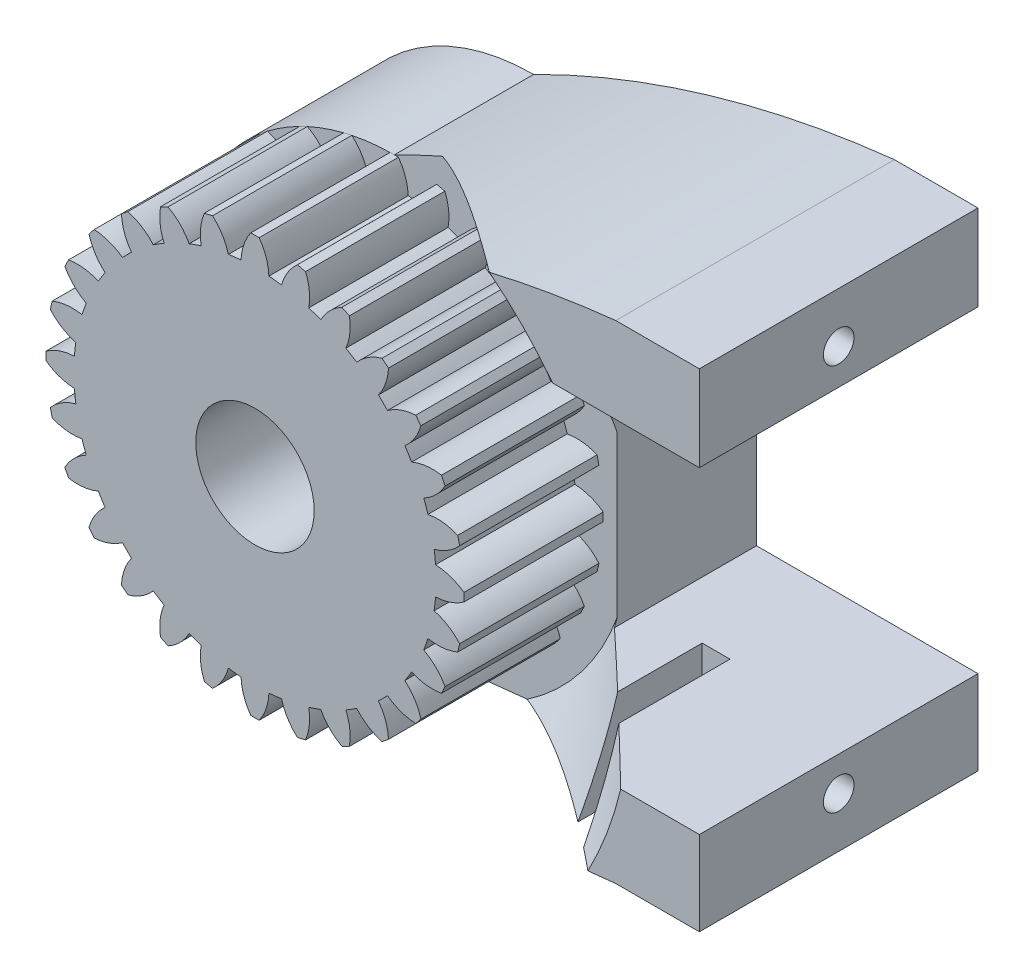
SolidWorks part; units mm, degrees
ref_plane "Front Plane" through (0, 0, 0) normal (0, 0, 1) x (1, 0, 0)
ref_plane "Top Plane" through (0, 0, 0) normal (0, 1, 0) x (1, 0, 0)
ref_plane "Right Plane" through (0, 0, 0) normal (1, 0, 0) x (0, 0, -1)
sketch "Sketch2" plane through (0, 0, 0) normal (0, 0, 1) x (1, 0, 0)
  line L0 (0, 0) -> (0, 18.136) construction
  line L1 (0.3, 15) -> (-0.3, 15)
  circle A0 centre (0, 0) radius 13
  circle A1 centre (0, 0) radius 4.25
  circle A2 centre (0, 0) radius 15 construction
  arc A3 (-0.3, 15) -> (-1, 12.9615) centre (2.738, 12.8174) ccw
  arc A4 (0.3, 15) -> (1, 12.9615) centre (-2.738, 12.8174) cw
  point P11 (-0.8, 14.0322)
  point P13 (0, 15)
  dimension "D1" = 26
  dimension "D2" = 8.5
  dimension "D6" = 0.8
  dimension "D7" = 30
  dimension "D4" = 0.6
  dimension "D5" = 1
  dimension "D3" = 2
extrude "Boss-Extrude1" add sketch "Sketch2" along normal blind 10 contours A0 A1 region at (9.2696, 8.582, 0)
extrude "Boss-Extrude2" add sketch "Sketch2<3>" along normal blind 10 contours A4 L1 A3 A0 region at (0, 13.8421, 0)
sketch "Sketch2<3>" plane through (0, 0, 0) normal (0, 0, 1) x (1, 0, 0) same geometry as "Sketch2"
pattern_circular "CirPattern1" count 28 over 360 about axis through (0, 0, 10) along (0, 0, 1) of "Boss-Extrude2"
sketch "Sketch3" plane through (0, 0, 10) normal (0, 0, 1) x (1, 0, 0)
  circle A0 centre (0, 0) radius 15
  circle A1 centre (0, 0) radius 7.5
  dimension "D1" = 30
  dimension "D2" = 15
extrude "Boss-Extrude3" add sketch "Sketch3" along normal blind 10
sketch "Sketch5" plane through (0, 0, 10) normal (0, 0, 1) x (1, 0, 0)
  circle A0 centre (0, 0) radius 4.25
  circle A1 centre (0, 0) radius 7.5
extrude "Boss-Extrude4" add sketch "Sketch5" along normal blind 5
sketch "Sketch6" plane through (0, 0, 20) normal (0, 0, 1) x (1, 0, 0)
  line L0 (0, 0) -> (16, 0) construction
  line L4 (42.95, -6.1) -> (16.2, -6.1) construction
  line L5 (72.2526, -52.0805) -> (45.5026, -52.0805)
  line L6 (72.2526, -52.0805) -> (72.2526, -39.8805)
  line L7 (72.2526, -39.8805) -> (45.5026, -39.8805)
  line L8 (45.5026, -52.0805) -> (45.5026, -39.8805)
  line L9 (72.2526, -52.0805) -> (45.5026, -39.8805) construction
  line L10 (72.2526, -39.8805) -> (45.5026, -52.0805) construction
  line L11 (42.95, -6.1) -> (42.95, 16.4) construction
  line L12 (42.95, 16.4) -> (16.2, 16.4) construction
  line L13 (16.2, -6.1) -> (16.2, 16.4) construction
  line L14 (42.95, -6.1) -> (16.2, 16.4) construction
  line L15 (42.95, 16.4) -> (16.2, -6.1) construction
  line L16 (0, 5.15) -> (50.833, 5.15) construction
  line L17 (0, 9.8857) -> (0, -10.1143) construction
  line L18 (43.15, 16.5) -> (16, 16.5)
  line L19 (16, -6.3) -> (16, 16.5)
  line L20 (43.15, -6.3) -> (16, -6.3)
  line L21 (43.15, -6.3) -> (43.15, 16.5)
  line L22 (31.5314, 22.65) -> (31.5314, 20.5) construction
  line L23 (31.9, -12.35) -> (25.9, -12.35)
  line L24 (31.9, -12.35) -> (31.9, 22.65)
  line L25 (31.9, 22.65) -> (25.9, 22.65)
  line L26 (25.9, -12.35) -> (25.9, 22.65)
  line L27 (31.9, -12.35) -> (25.9, 22.65) construction
  line L28 (31.9, 22.65) -> (25.9, -12.35) construction
  line L29 (18.9976, 0) -> (49.2209, 0) construction
  line L30 (25.9, -12.35) -> (2.0604, -14.8578)
  line L31 (16, -6.3) -> (13.6129, -6.3)
  arc A1 (25.9, 22.65) -> (0, 15) centre (33.848, -51.9277) ccw
  arc A2 (0, 15) -> (0, -15) centre (0, 0) cw
  circle A3 centre (0, 0) radius 15 construction
  point P1 (58.8776, -45.9805)
  point P12 (29.575, 5.15)
  point P29 (28.9, 5.15)
  circle M3 centre (0, 0) radius 15
  dimension "D2" = 12.2
  dimension "D14" = 16
  dimension "D15" = 75
  dimension "D1" = 26.75
  dimension "D3" = 26.75
  dimension "D4" = 22.5
  dimension "D5" = 15.7
  dimension "D6" = 35
  dimension "D7" = 2.15
  dimension "D8" = 6
  dimension "D9" = 6.1
  dimension "D10" = 0.2
  dimension "D11" = 0.2
  dimension "D12" = 0.2
  dimension "D13" = 0.2
sketch "Sketch11" plane through (0, 0, 0) normal (0, 1, 0) x (1, 0, 0)
  line L0 (72.2526, -20) -> (45.5026, -20) construction
  line L1 (45.1876, -16.1) -> (18.4376, -16.1) construction
  line L2 (45.1876, -16.1) -> (45.1876, 6.4) construction
  line L3 (45.1876, 6.4) -> (18.4376, 6.4) construction
  line L4 (18.4376, -16.1) -> (18.4376, 6.4) construction
  line L5 (45.1876, -16.1) -> (18.4376, 6.4) construction
  line L6 (45.1876, 6.4) -> (18.4376, -16.1) construction
  line L7 (0, -4.85) -> (48.8951, -4.85) construction
  line L8 (0, 0) -> (0, -20) construction
  line L9 (0, -20) -> (16, -20) construction
  line L10 (45.3876, 6.6) -> (18.2376, 6.6)
  line L11 (18.2376, -16.3) -> (18.2376, 6.6)
  line L12 (45.3876, -16.3) -> (18.2376, -16.3)
  line L13 (45.3876, -16.3) -> (45.3876, 6.6)
  line L14 (33.7357, 11.2) -> (33.7357, 9.05) construction
  line L15 (34.1376, -20.9) -> (28.1376, -20.9)
  line L16 (34.1376, -20.9) -> (34.1376, 11.2)
  line L17 (34.1376, 11.2) -> (28.1376, 11.2)
  line L18 (28.1376, -20.9) -> (28.1376, 11.2)
  line L19 (34.1376, -20.9) -> (28.1376, 11.2) construction
  line L20 (34.1376, 11.2) -> (28.1376, -20.9) construction
  line L21 (17.0596, -10) -> (47.283, -10) construction
  point P0 (31.8126, -4.85)
  point P24 (31.1376, -4.85)
  dimension "D1" = 26.75
  dimension "D2" = 22.5
  dimension "D4" = 15.7
  dimension "D5" = 32.1
  dimension "D6" = 2.15
  dimension "D7" = 6
  dimension "D8" = 6.1
  dimension "D3" = 0.2
extrude "Boss-Extrude7" add sketch "Sketch6" against normal blind 10 contours L26 A1 L31 L19 L18 M3 | L26 L18 L24 L25 | L20 L31 L30 L26 M3 | L26 L23 L24 L20 region at (28.9, 19.575, 20) region at (14.6392, 14.3925, 20) region at (28.9, -9.325, 20) region at (17.5515, -10.1768, 20)
sketch "Sketch12" plane through (0, 0, 10) normal (0, 0, -1) x (-1, 0, 0)
  line L0 (-25.9, 22.65) -> (-31.9, 22.65)
  line L1 (-31.9, 22.65) -> (-31.9, 16.5)
  line L2 (-31.9, 16.5) -> (-16, 16.5)
  line L3 (-16, 16.5) -> (-16, 5.7446)
  line L4 (-16, -6.3) -> (-16, 16.5) construction
  line L5 (-16, -5.7446) -> (-16, -6.3)
  line L6 (-16, -6.3) -> (-31.9, -6.3)
  line L7 (-31.9, -6.3) -> (-31.9, -12.35)
  line L8 (-31.9, -12.35) -> (-25.9, -12.35)
  line L9 (-25.9, -12.35) -> (-9.5397, -14.071)
  line L10 (-25.9, -12.35) -> (-2.0604, -14.8578) construction
  circle A0 centre (0, 0) radius 17
  arc A1 (-25.9, 22.65) -> (-3.4659, 16.6429) centre (-33.848, -51.9277) cw
  arc A2 (0, 15) -> (-25.9, 22.65) centre (-33.848, -51.9277) ccw construction
  dimension "D1" = 34
extrude "Boss-Extrude8" add sketch "Sketch12" along normal blind 10 contours A1 L0 L1 L2 L3 A0 | A0 L5 L6 L7 L8 L9 region at (18.9294, 17.6106, 10) region at (22.2103, -9.7895, 10)
chamfer "Chamfer1" distance 10 angle 45 2 edges at (13.4314, -10.421, 0) (11.1546, 12.8287, 0)
mirror "Mirror1" about plane through (0, 0, 0) normal (0, 0, 1) of bodies 118
sketch "Sketch13" plane through (0, 0, 20) normal (0, 0, 1) x (1, 0, 0)
  line L1 (-37.7735, 30.5558) -> (48.8875, 30.5558)
  line L2 (-37.7735, 30.5558) -> (-37.7735, -27.2801)
  line L3 (-37.7735, -27.2801) -> (48.8875, -27.2801)
  line L4 (48.8875, 30.5558) -> (48.8875, -27.2801)
  line L5 (-37.7735, 30.5558) -> (48.8875, -27.2801) construction
  line L6 (-37.7735, -27.2801) -> (48.8875, 30.5558) construction
  point P0 (5.557, 1.6379)
extrude "Cut-Extrude1" cut sketch "Sketch13" against normal blind 20
sketch "Sketch14" plane through (31.9, 0, 0) normal (1, 0, 0) x (0, 0, -1)
  line L0 (10, 22.65) -> (10, -12.35) construction
  line L1 (20, 22.65) -> (0, 22.65) construction
  line L2 (20, -12.35) -> (0, -12.35) construction
  line L3 (10, 5.15) -> (21.6897, 5.15) construction
  line L4 (4.0163, 16.5) -> (20, 16.5) construction
  circle A0 centre (10, 19.05) radius 1.1
  circle A2 centre (10, -8.75) radius 1.1
  dimension "D3" = 2.2
  dimension "D1" = 6.15
  dimension "D2" = 27.8
extrude "Cut-Extrude2" cut sketch "Sketch14" against normal blind 2
sketch "Sketch15" plane through (0, -6.3, 0) normal (0, 1, 0) x (1, 0, 0)
  line L0 (31.9, 10) -> (29.1759, 10) construction
  line L1 (20.1, 12) -> (22.1, 12)
  line L2 (20.1, 12) -> (20.1, -0.8515)
  line L3 (20.1, -0.8515) -> (22.1, -0.8515)
  line L4 (22.1, 12) -> (22.1, -0.8515)
  line L5 (20.1, 12) -> (22.1, -0.8515) construction
  line L6 (20.1, -0.8515) -> (22.1, 12) construction
  line L7 (31.9, 20) -> (31.9, 0) construction
  line L8 (21.1, 12) -> (21.1, 8.453) construction
  point P0 (21.1, 5.5743)
  dimension "D1" = 2
  dimension "D2" = 10.8
  dimension "D3" = 2
extrude "Cut-Extrude3" cut sketch "Sketch15" against normal through all
sketch "Sketch16" plane through (0, 0, -20) normal (0, 0, -1) x (-1, 0, 0)
  circle A0 centre (0, 0) radius 9.5
  dimension "D1" = 19
extrude "Cut-Extrude4" cut sketch "Sketch16" against normal up to surface (5 mm away) up to face at (7.5, 0, -15)
